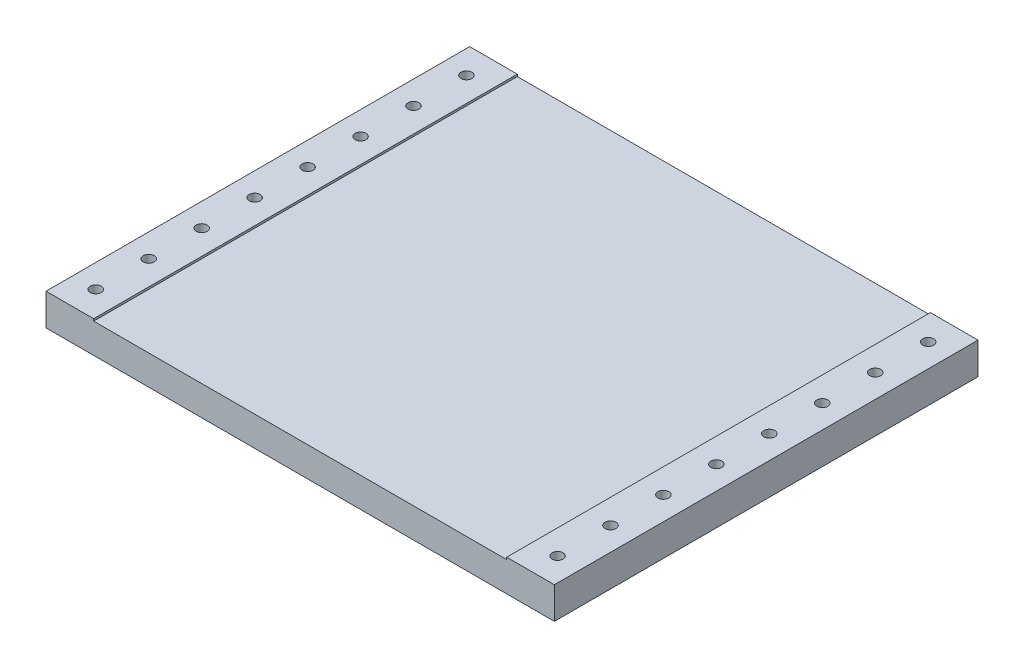
SolidWorks part; units mm, degrees
ref_plane "Front Plane" through (0, 0, 0) normal (0, 0, 1) x (1, 0, 0)
ref_plane "Top Plane" through (0, 0, 0) normal (0, 1, 0) x (1, 0, 0)
ref_plane "Right Plane" through (0, 0, 0) normal (1, 0, 0) x (0, 0, -1)
sketch "Sketch1" plane through (0, 0, 0) normal (0, 1, 0) x (1, 0, 0)
  line L1 (-120, -100) -> (120, -100)
  line L2 (-120, -100) -> (-120, 100)
  line L3 (-120, 100) -> (120, 100)
  line L4 (120, -100) -> (120, 100)
  line L5 (-120, -100) -> (120, 100) construction
  line L6 (-120, 100) -> (120, -100) construction
  point P0 (0, 0)
  dimension "D1" = 240
  dimension "D2" = 200
extrude "Boss-Extrude1" add sketch "Sketch1" along normal mid plane 15
sketch "Sketch3" plane through (0, 7.5, 0) normal (0, 1, 0) x (1, 0, 0)
  line L1 (-92.5, -105) -> (92.5, -105)
  line L2 (-97.5, -100) -> (-97.5, 100)
  line L3 (-92.5, 105) -> (92.5, 105)
  line L4 (97.5, -100) -> (97.5, 100)
  line L5 (-97.5, -105) -> (97.5, 105) construction
  line L6 (-97.5, 105) -> (97.5, -105) construction
  arc A0 (-92.5, -105) -> (-97.5, -100) centre (-92.5, -100) cw
  arc A1 (97.5, -100) -> (92.5, -105) centre (92.5, -100) cw
  arc A2 (97.5, 100) -> (92.5, 105) centre (92.5, 100) ccw
  arc A3 (-92.5, 105) -> (-97.5, 100) centre (-92.5, 100) ccw
  point P0 (0, 0)
  dimension "D3" = 5
  dimension "D1" = 195
  dimension "D2" = 210
extrude "Cut-Extrude2" cut sketch "Sketch3" against normal blind 1
sketch "Sketch4" plane through (0, 7.5, 0) normal (0, 1, 0) x (1, 0, 0)
  line L0 (-109, -1033.7087) -> (-109, 48966.2913) construction
  line L1 (109, -1052.3781) -> (109, 48947.6219) construction
  line L2 (-1012.9649, 87.5) -> (48987.0351, 87.5) construction
  line L3 (-97.5, 100) -> (97.5, 100) construction
  line L4 (-120, 100) -> (-120, -100) construction
  line L5 (120, -100) -> (120, 100) construction
  circle A0 centre (-109, 87.5) radius 2.6
  circle A1 centre (109, 87.5) radius 2.6
  dimension "D4" = 5.2
  dimension "D5" = 5.2
  dimension "D1" = 12.5
  dimension "D2" = 11
  dimension "D3" = 11
extrude "Cut-Extrude3" cut sketch "Sketch4" against normal through all
pattern_linear "LPattern1" count 8 spacing 25 along (0, 0, 1) of "Cut-Extrude3"
